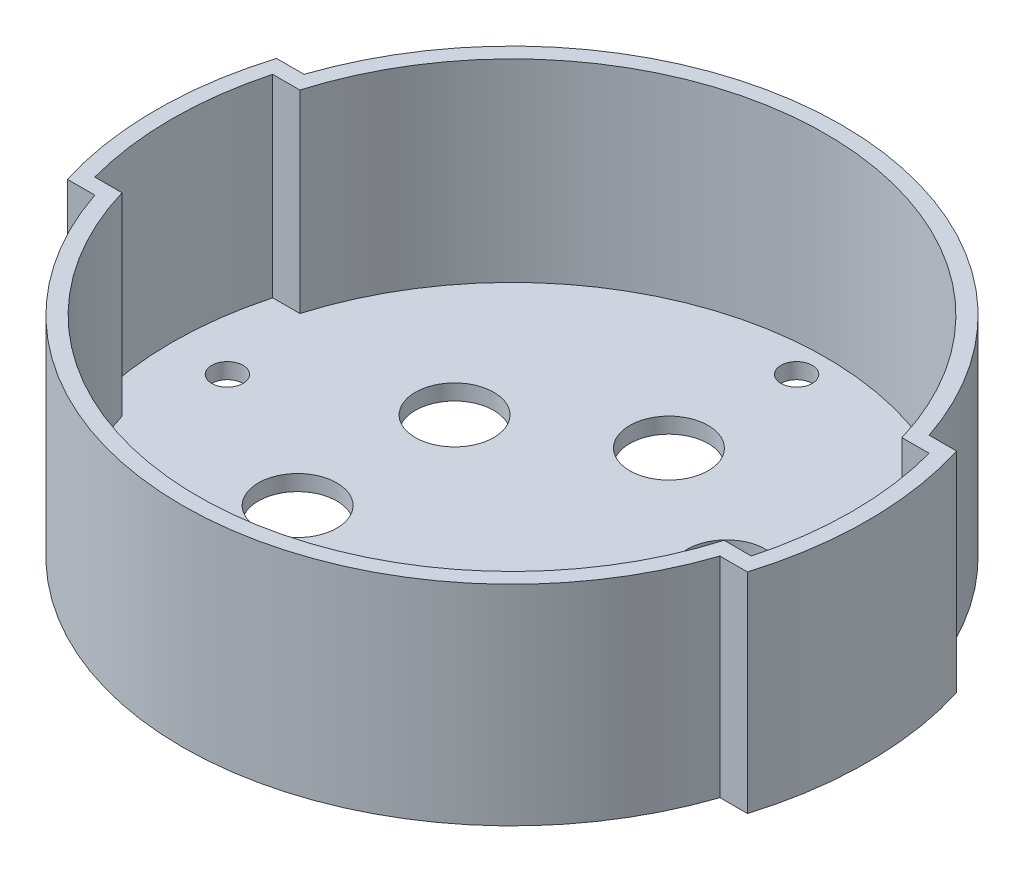
SolidWorks part; units mm, degrees
ref_plane "Front Plane" through (0, 0, 0) normal (0, 0, 1) x (1, 0, 0)
ref_plane "Top Plane" through (0, 0, 0) normal (0, 1, 0) x (1, 0, 0)
ref_plane "Right Plane" through (0, 0, 0) normal (1, 0, 0) x (0, 0, -1)
sketch "Sketch1" plane through (0, 0, 0) normal (0, 1, 0) x (1, 0, 0)
  circle A0 centre (0, 0) radius 68
  dimension "D1" = 136
extrude "Boss-Extrude1" add sketch "Sketch1" along normal blind 40
sketch "Sketch2" plane through (0, 40, 0) normal (0, 1, 0) x (1, 0, 0)
  line L1 (0, 37.0764) -> (0, -27.4787) construction
  line L5 (-59.7411, -20) -> (-64.9923, -20)
  line L6 (-59.7411, 20) -> (-64.9923, 20)
  line L7 (59.7411, -20) -> (64.9923, -20)
  line L8 (59.7411, 20) -> (64.9923, 20)
  line L9 (-28.4675, 0) -> (19.3594, 0) construction
  arc A0 (-59.7411, -20) -> (59.7411, -20) centre (0, 0) ccw
  arc A1 (-64.9923, -20) -> (64.9923, -20) centre (0, 0) ccw
  circle A2 centre (0, 0) radius 68 construction
  arc A3 (59.7411, 20) -> (-59.7411, 20) centre (0, 0) ccw
  arc A4 (64.9923, 20) -> (-64.9923, 20) centre (0, 0) ccw
  dimension "D1" = 126
  dimension "D2" = 40
  dimension "D3" = 40
extrude "Cut-Extrude1" cut sketch "Sketch2" against normal up to surface (40 mm away) up to face at (0, 0, 68)
shell "Shell1" thickness 3 removed face at (0, 40, 0)
sketch "Sketch3" plane through (0, 0, 0) normal (0, -1, 0) x (1, 0, 0)
  line L0 (-78.2757, 0) -> (93.912, 0) construction
  line L1 (0, -51.8142) -> (0, 50.9292) construction
  circle A0 centre (-54.4, 0) radius 3
  circle A1 centre (54.4, 0) radius 3
  circle A2 centre (0, 30) radius 7.5
  circle A3 centre (25.9808, 15) radius 7.5
  circle A4 centre (25.9808, -15) radius 7.5
  circle A5 centre (0, -30) radius 7.5
  circle A6 centre (-25.9808, -15) radius 7.5
  circle A7 centre (-25.9808, 15) radius 7.5
  circle A8 centre (0, -54.4) radius 3
  circle A9 centre (0, 54.4) radius 3
  point P24 (0, 0)
  dimension "D1" = 6
  dimension "D2" = 6
  dimension "D5" = 15
  dimension "D9" = 6
  dimension "D10" = 6
  dimension "D3" = 54.4
  dimension "D4" = 54.4
  dimension "D6" = 30
  dimension "D8" = 30
  dimension "D11" = 54.4
  dimension "D12" = 54.4
  dimension "D7" = 6
extrude "Cut-Extrude2" cut sketch "Sketch3" against normal through all both and the other way through all
